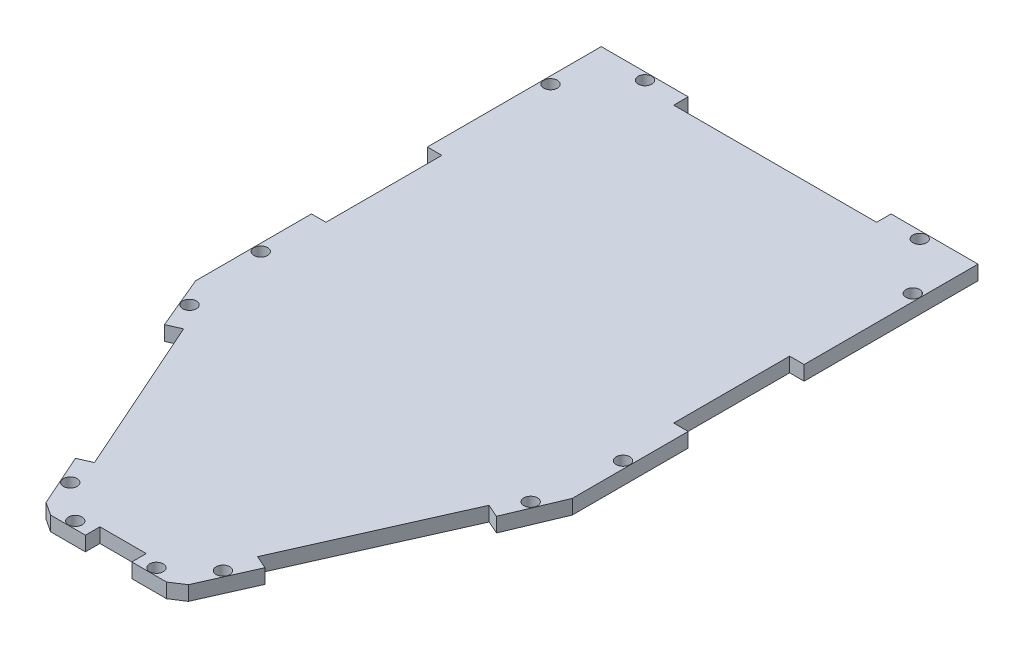
SolidWorks part; units mm, degrees
ref_plane "Front Plane" through (0, 0, 0) normal (0, 0, 1) x (1, 0, 0)
ref_plane "Top Plane" through (0, 0, 0) normal (0, 1, 0) x (1, 0, 0)
ref_plane "Right Plane" through (0, 0, 0) normal (1, 0, 0) x (0, 0, -1)
sketch "Sketch1" plane through (0, 0, 0) normal (0, 1, 0) x (1, 0, 0)
  line L0 (-41.275, 0) -> (-36.3683, -11.7139)
  line L1 (22.225, 85.725) -> (-22.225, 85.725)
  line L3 (-41.275, 88.9) -> (-22.225, 88.9)
  line L4 (22.225, 88.9) -> (22.225, 85.725)
  line L5 (41.275, 50.8) -> (41.275, 88.9)
  line L6 (-41.275, 0) -> (-38.1, 0) construction
  line L7 (-41.275, 50.8) -> (-38.1, 50.8)
  line L8 (0, 63.5) -> (0, -63.5) construction
  line L9 (38.1, 50.8) -> (38.1, 25.4)
  line L10 (-38.1, 50.8) -> (-38.1, 25.4)
  line L11 (-41.275, 50.8) -> (-41.275, 88.9)
  line L12 (41.275, 50.8) -> (38.1, 50.8)
  line L13 (-22.225, 88.9) -> (-22.225, 85.725)
  line L16 (41.275, 88.9) -> (22.225, 88.9)
  line L17 (-41.275, 0) -> (41.275, 0) construction
  line L18 (-38.1, 0) -> (-38.1, 25.4) construction
  line L19 (-38.1, 25.4) -> (-41.275, 25.4)
  line L21 (-41.275, 0) -> (-41.275, 25.4)
  line L22 (38.1, 25.4) -> (41.275, 25.4)
  line L23 (-38.1, 0) -> (-33.467, -10.4244) construction
  line L24 (41.275, 0) -> (41.275, 25.4)
  line L25 (33.467, -10.4244) -> (38.1, 0) construction
  line L26 (-36.3683, -11.7139) -> (-33.467, -10.4244) construction
  line L27 (41.275, 0) -> (36.3683, -11.7139)
  line L28 (36.3683, -11.7139) -> (33.467, -10.4244) construction
  line L29 (-17.858, -45.5446) -> (-12.7, -57.15) construction
  line L30 (-12.7, -57.15) -> (-15.6014, -58.4395) construction
  line L31 (-17.858, -45.5446) -> (-20.7593, -46.8341)
  line L32 (-15.6014, -58.4395) -> (-20.7593, -46.8341)
  line L33 (12.7, -57.15) -> (17.858, -45.5446) construction
  line L34 (-33.467, -10.4244) -> (-17.858, -45.5446)
  line L35 (-12.7, -57.15) -> (12.7, -57.15) construction
  line L36 (17.858, -45.5446) -> (33.467, -10.4244)
  line L38 (41.275, 69.85) -> (-41.275, 69.85) construction
  line L39 (12.7, -57.15) -> (15.6014, -58.4395) construction
  line L40 (17.858, -45.5446) -> (20.7593, -46.8341)
  line L41 (15.6014, -58.4395) -> (20.7593, -46.8341)
  line L42 (38.1, 0) -> (38.1, 25.4) construction
  line L43 (-15.6014, -58.4395) -> (-12.7, -60.325)
  line L44 (-5.08, -57.15) -> (-12.7, -57.15) construction
  line L45 (-5.08, -57.15) -> (-5.08, -60.325)
  line L46 (-5.08, -60.325) -> (-12.7, -60.325)
  line L47 (-12.7, -57.15) -> (-12.7, -60.325) construction
  line L48 (5.08, -57.15) -> (12.7, -57.15) construction
  line L49 (5.08, -57.15) -> (5.08, -60.325)
  line L50 (5.08, -60.325) -> (12.7, -60.325)
  line L51 (12.7, -57.15) -> (12.7, -60.325) construction
  line L52 (15.6014, -58.4395) -> (12.7, -60.325)
  line L53 (-5.08, -57.15) -> (5.08, -57.15)
  line L54 (33.467, -10.4244) -> (36.3683, -11.7139)
  line L55 (-33.467, -10.4244) -> (-36.3683, -11.7139)
  point P0 (0, 0)
  point P1 (0, -57.15)
  dimension "D1" = 25.4
  dimension "D2" = 57.15
  dimension "D3" = 3.175
  dimension "D4" = 82.55
  dimension "D5" = 3.175
  dimension "D6" = 19.05
  dimension "D8" = 38.1
  dimension "D9" = 50.8
  dimension "D10" = 25.4
  dimension "D11" = 12.7
  dimension "D12" = 12.7
  dimension "D13" = 10.16
extrude "Boss-Extrude1" add sketch "Sketch1" along normal blind 3.175
sketch "Sketch2" plane through (0, 0, 0) normal (0, -1, 0) x (-1, 0, 0)
  line L0 (39.6875, 50.8) -> (39.6875, 88.9) construction
  line L1 (41.275, 50.8) -> (38.1, 50.8) construction
  line L2 (22.225, 88.9) -> (41.275, 88.9) construction
  line L3 (0, 85.725) -> (0, -57.15) construction
  line L5 (41.275, 0) -> (36.3683, -11.7139) construction
  line L6 (-5.08, -58.7375) -> (-15.1428, -58.7375) construction
  line L7 (5.08, -57.15) -> (-5.08, -57.15) construction
  line L8 (-22.225, 85.725) -> (22.225, 85.725) construction
  line L10 (22.225, 88.9) -> (41.275, 88.9) construction
  line L11 (39.6875, 25.4) -> (39.6875, -3.7899) construction
  line L12 (38.1, 25.4) -> (41.275, 25.4) construction
  line L15 (41.275, 0) -> (36.3683, -11.7139) construction
  line L18 (34.9176, -11.0691) -> (41.275, 4.108) construction
  line L23 (36.3683, -11.7139) -> (33.467, -10.4244) construction
  line L24 (41.275, 25.4) -> (41.275, 0) construction
  line L25 (19.3086, -46.1893) -> (13.0261, -60.325) construction
  line L26 (17.858, -45.5446) -> (20.7593, -46.8341) construction
  line L27 (12.7, -60.325) -> (5.08, -60.325) construction
  line L28 (5.08, -58.7375) -> (15.1428, -58.7375) construction
  line L29 (5.08, -60.325) -> (5.08, -57.15) construction
  line L30 (15.6014, -58.4395) -> (12.7, -60.325) construction
  line L31 (-19.3086, -46.1893) -> (-13.0261, -60.325) construction
  line L32 (-34.9176, -11.0691) -> (-41.275, 4.108) construction
  line L33 (-39.6875, 25.4) -> (-39.6875, -3.7899) construction
  line L34 (-39.6875, 50.8) -> (-39.6875, 88.9) construction
  circle A0 centre (39.6875, 76.2) radius 1.5
  circle A1 centre (-8.89, -58.7375) radius 1.5
  circle A2 centre (39.6875, 12.7) radius 1.5
  circle A3 centre (37.3715, -5.2108) radius 1.5
  circle A4 centre (16.7297, -51.992) radius 1.5
  circle A5 centre (8.89, -58.7375) radius 1.5
  circle A6 centre (-16.7297, -51.992) radius 1.5
  circle A7 centre (-37.3715, -5.2108) radius 1.5
  circle A8 centre (-39.6875, 12.7) radius 1.5
  circle A9 centre (-39.6875, 76.2) radius 1.5
  dimension "D1" = 3
  dimension "D4" = 6.35
  dimension "D6" = 3.81
  dimension "D2" = 3
  dimension "D3" = 12.7
  dimension "D5" = 6.35
  dimension "D7" = 12.7
extrude "Cut-Extrude1" cut sketch "Sketch2" against normal through all
sketch "Sketch3" plane through (0, 0, 0) normal (0, -1, 0) x (1, 0, 0)
  line L0 (22.225, -87.3125) -> (41.275, -87.3125) construction
  line L1 (22.225, -88.9) -> (22.225, -85.725) construction
  line L2 (41.275, -50.8) -> (41.275, -88.9) construction
  line L3 (-22.225, -87.3125) -> (-41.275, -87.3125) construction
  line L4 (-22.225, -85.725) -> (-22.225, -88.9) construction
  line L5 (-41.275, -88.9) -> (-41.275, -50.8) construction
  circle A0 centre (-30.099, -87.3125) radius 1.5
  circle A1 centre (30.099, -87.3125) radius 1.5
  dimension "D1" = 3
  dimension "D2" = 7.874
  dimension "D3" = 7.874
extrude "Cut-Extrude2" cut sketch "Sketch3" against normal through all
